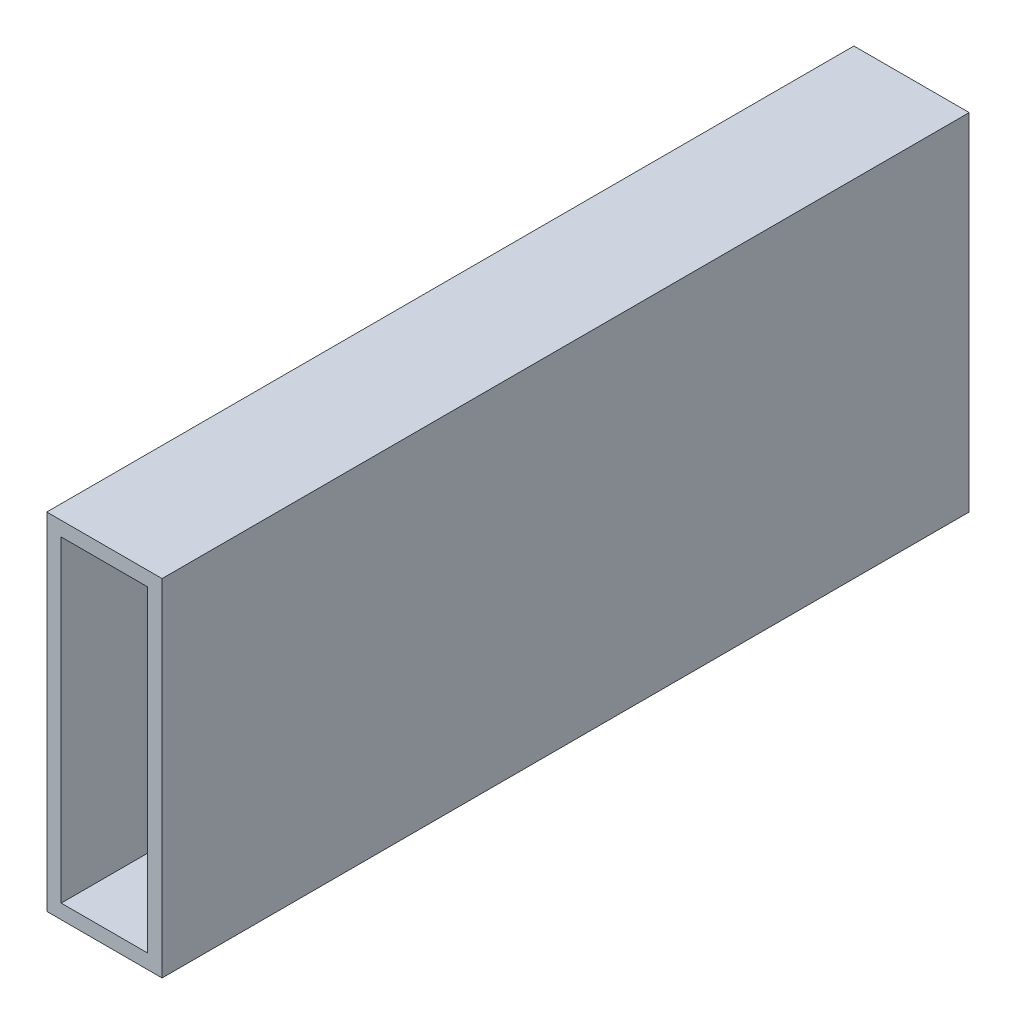
SolidWorks part; units mm, degrees
ref_plane "Front Plane" through (0, 0, 0) normal (0, 0, 1) x (1, 0, 0)
ref_plane "Top Plane" through (0, 0, 0) normal (0, 1, 0) x (1, 0, 0)
ref_plane "Right Plane" through (0, 0, 0) normal (1, 0, 0) x (0, 0, -1)
sketch "Sketch1" plane through (0, 0, 0) normal (0, 0, 1) x (1, 0, 0)
  line L1 (-12.7, -38.1) -> (12.7, -38.1)
  line L2 (-12.7, -38.1) -> (-12.7, 38.1)
  line L3 (-12.7, 38.1) -> (12.7, 38.1)
  line L4 (12.7, -38.1) -> (12.7, 38.1)
  line L5 (-12.7, -38.1) -> (12.7, 38.1) construction
  line L6 (-12.7, 38.1) -> (12.7, -38.1) construction
  point P0 (0, 0)
  dimension "D1" = 25.4
  dimension "D2" = 76.2
extrude "Boss-Extrude1" add sketch "Sketch1" along normal mid plane 177.8
shell "Shell1" thickness 3.175 removed face at (0, 0, -88.9) removed face at (0, 0, 88.9)
